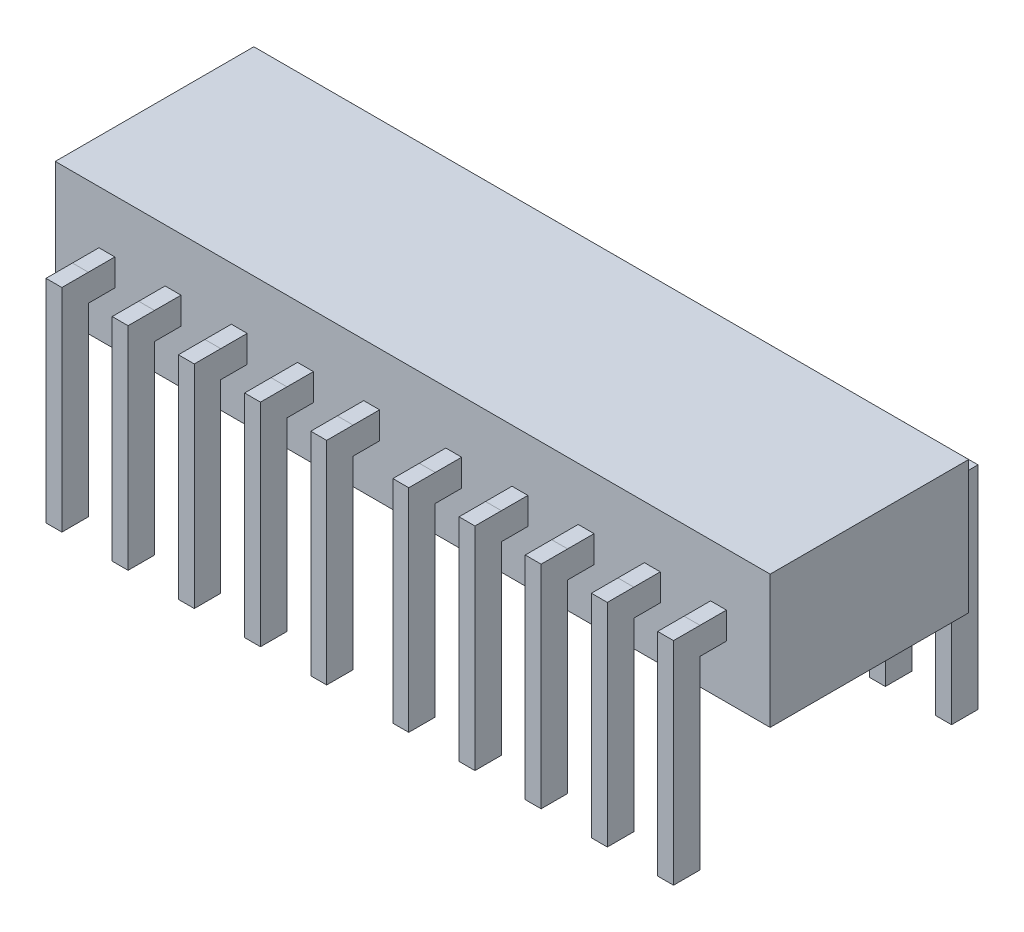
SolidWorks part; units mm, degrees
ref_plane "Front Plane" through (0, 0, 0) normal (0, 0, 1) x (1, 0, 0)
ref_plane "Top Plane" through (0, 0, 0) normal (0, 1, 0) x (1, 0, 0)
ref_plane "Right Plane" through (0, 0, 0) normal (1, 0, 0) x (0, 0, -1)
sketch "Sketch1" plane through (0, 0, 0) normal (0, 1, 0) x (1, 0, 0)
  line L0 (-13500, -3750) -> (13500, -3750)
  line L1 (-13500, -3750) -> (-13500, 3750)
  line L2 (-13500, 3750) -> (13500, 3750)
  line L3 (13500, 3750) -> (13500, -3750)
  line L4 (-11250, 5750) -> (-11850, 5750)
  line L5 (11850, -4750) -> (11850, -5750)
  line L6 (11850, -4750) -> (11250, -4750)
  line L7 (1250, -5750) -> (1250, -3750)
  line L8 (1250, -5750) -> (1850, -5750)
  line L9 (1850, -5750) -> (1850, -3750)
  line L10 (3750, -5750) -> (4350, -5750)
  line L11 (3750, -5750) -> (3750, -3750)
  line L12 (6250, -5750) -> (6850, -5750)
  line L13 (4350, -5750) -> (4350, -3750)
  line L14 (8750, -5750) -> (9350, -5750)
  line L15 (6250, -5750) -> (6250, -3750)
  line L16 (11250, -5750) -> (11850, -5750)
  line L17 (6850, -5750) -> (6850, -3750)
  line L18 (8750, -5750) -> (8750, -3750)
  line L19 (9350, -5750) -> (9350, -3750)
  line L20 (-11850, -5750) -> (-11850, -3750)
  line L21 (-11250, -5750) -> (-11250, -3750)
  line L22 (-9350, -5750) -> (-9350, -3750)
  line L23 (-8750, -5750) -> (-8750, -3750)
  line L24 (-6850, -5750) -> (-6850, -3750)
  line L25 (-11250, -5750) -> (-11850, -5750)
  line L26 (-6250, -5750) -> (-6250, -3750)
  line L27 (-8750, -5750) -> (-9350, -5750)
  line L28 (-4350, -5750) -> (-4350, -3750)
  line L29 (-6250, -5750) -> (-6850, -5750)
  line L30 (-3750, -5750) -> (-3750, -3750)
  line L31 (-3750, -5750) -> (-4350, -5750)
  line L32 (-1850, -5750) -> (-1850, -3750)
  line L33 (-1250, -5750) -> (-1850, -5750)
  line L34 (-1250, -5750) -> (-1250, -3750)
  line L35 (11250, -5750) -> (11250, -3750)
  line L36 (-1250, 5750) -> (-1250, 3750)
  line L37 (-1250, 5750) -> (-1850, 5750)
  line L38 (-1850, 5750) -> (-1850, 3750)
  line L39 (-3750, 5750) -> (-4350, 5750)
  line L40 (-3750, 5750) -> (-3750, 3750)
  line L41 (-6250, 5750) -> (-6850, 5750)
  line L42 (-4350, 5750) -> (-4350, 3750)
  line L43 (-8750, 5750) -> (-9350, 5750)
  line L44 (-6250, 5750) -> (-6250, 3750)
  line L45 (11850, -5750) -> (11850, -3750)
  line L46 (-6850, 5750) -> (-6850, 3750)
  line L47 (-8750, 5750) -> (-8750, 3750)
  line L48 (-9350, 5750) -> (-9350, 3750)
  line L49 (-11250, 5750) -> (-11250, 3750)
  line L50 (-11850, 5750) -> (-11850, 3750)
  line L51 (11850, 5750) -> (11850, 3750)
  line L52 (11250, 5750) -> (11250, 3750)
  line L53 (9350, 5750) -> (9350, 3750)
  line L54 (8750, 5750) -> (8750, 3750)
  line L55 (6850, 5750) -> (6850, 3750)
  line L56 (11250, 5750) -> (11850, 5750)
  line L57 (6250, 5750) -> (6250, 3750)
  line L58 (8750, 5750) -> (9350, 5750)
  line L59 (4350, 5750) -> (4350, 3750)
  line L60 (6250, 5750) -> (6850, 5750)
  line L61 (3750, 5750) -> (3750, 3750)
  line L62 (3750, 5750) -> (4350, 5750)
  line L63 (1850, 5750) -> (1850, 3750)
  line L64 (1250, 5750) -> (1850, 5750)
  line L65 (1250, 5750) -> (1250, 3750)
  line L66 (11250, -5750) -> (11250, -4750)
  line L68 (9350, -4750) -> (9350, -5750)
  line L69 (9350, -4750) -> (8750, -4750)
  line L70 (8750, -5750) -> (9350, -5750)
  line L71 (8750, -5750) -> (8750, -4750)
  line L72 (6850, -4750) -> (6850, -5750)
  line L73 (6850, -4750) -> (6250, -4750)
  line L74 (6250, -5750) -> (6850, -5750)
  line L75 (6250, -5750) -> (6250, -4750)
  line L76 (1850, -4750) -> (1850, -5750)
  line L77 (1850, -4750) -> (1250, -4750)
  line L78 (1250, -5750) -> (1850, -5750)
  line L79 (1250, -5750) -> (1250, -4750)
  line L80 (4350, -4750) -> (4350, -5750)
  line L81 (4350, -4750) -> (3750, -4750)
  line L82 (3750, -5750) -> (4350, -5750)
  line L83 (3750, -5750) -> (3750, -4750)
  line L84 (-1250, -4750) -> (-1250, -5750)
  line L85 (-1250, -4750) -> (-1850, -4750)
  line L86 (-11850, -5750) -> (-11250, -5750)
  line L87 (-9350, -5750) -> (-8750, -5750)
  line L88 (-6850, -5750) -> (-6250, -5750)
  line L89 (-4350, -5750) -> (-3750, -5750)
  line L90 (-1850, -5750) -> (-1250, -5750)
  line L91 (-1850, -5750) -> (-1850, -4750)
  line L92 (-3750, -4750) -> (-3750, -5750)
  line L93 (-3750, -4750) -> (-4350, -4750)
  line L94 (-4350, -5750) -> (-3750, -5750)
  line L95 (-4350, -5750) -> (-4350, -4750)
  line L96 (-6250, -4750) -> (-6250, -5750)
  line L97 (-6250, -4750) -> (-6850, -4750)
  line L98 (-6850, -5750) -> (-6250, -5750)
  line L99 (-6850, -5750) -> (-6850, -4750)
  line L100 (-11250, -4750) -> (-11250, -5750)
  line L101 (-11250, -4750) -> (-11850, -4750)
  line L102 (-11850, -5750) -> (-11250, -5750)
  line L103 (-11850, -5750) -> (-11850, -4750)
  line L104 (-8750, -4750) -> (-8750, -5750)
  line L105 (-8750, -4750) -> (-9350, -4750)
  line L106 (-9350, -5750) -> (-8750, -5750)
  line L107 (-9350, -5750) -> (-9350, -4750)
  line L108 (11850, 5750) -> (11850, 4750)
  line L109 (11850, 5750) -> (11250, 5750)
  line L110 (1250, 4750) -> (1850, 4750)
  line L111 (3750, 4750) -> (4350, 4750)
  line L112 (6250, 4750) -> (6850, 4750)
  line L113 (8750, 4750) -> (9350, 4750)
  line L114 (11250, 4750) -> (11850, 4750)
  line L115 (11250, 4750) -> (11250, 5750)
  line L116 (9350, 5750) -> (9350, 4750)
  line L117 (9350, 5750) -> (8750, 5750)
  line L118 (8750, 4750) -> (9350, 4750)
  line L119 (8750, 4750) -> (8750, 5750)
  line L120 (6850, 5750) -> (6850, 4750)
  line L121 (6850, 5750) -> (6250, 5750)
  line L122 (6250, 4750) -> (6850, 4750)
  line L123 (6250, 4750) -> (6250, 5750)
  line L124 (1850, 5750) -> (1850, 4750)
  line L125 (1850, 5750) -> (1250, 5750)
  line L126 (1250, 4750) -> (1850, 4750)
  line L127 (1250, 4750) -> (1250, 5750)
  line L128 (4350, 5750) -> (4350, 4750)
  line L129 (4350, 5750) -> (3750, 5750)
  line L130 (3750, 4750) -> (4350, 4750)
  line L131 (3750, 4750) -> (3750, 5750)
  line L132 (-1250, 5750) -> (-1250, 4750)
  line L133 (-1250, 5750) -> (-1850, 5750)
  line L134 (-11850, 4750) -> (-11250, 4750)
  line L135 (-9350, 4750) -> (-8750, 4750)
  line L136 (-6850, 4750) -> (-6250, 4750)
  line L137 (-4350, 4750) -> (-3750, 4750)
  line L138 (-1850, 4750) -> (-1250, 4750)
  line L139 (-1850, 4750) -> (-1850, 5750)
  line L140 (-3750, 5750) -> (-3750, 4750)
  line L141 (-3750, 5750) -> (-4350, 5750)
  line L142 (-4350, 4750) -> (-3750, 4750)
  line L143 (-4350, 4750) -> (-4350, 5750)
  line L144 (-6250, 5750) -> (-6250, 4750)
  line L145 (-6250, 5750) -> (-6850, 5750)
  line L146 (-6850, 4750) -> (-6250, 4750)
  line L147 (-6850, 4750) -> (-6850, 5750)
  line L148 (-11250, 5750) -> (-11250, 4750)
  line L149 (-11250, 5750) -> (-11850, 5750)
  line L150 (-11850, 4750) -> (-11250, 4750)
  line L151 (-11850, 4750) -> (-11850, 5750)
  line L152 (-8750, 5750) -> (-8750, 4750)
  line L153 (-8750, 5750) -> (-9350, 5750)
  line L154 (-9350, 4750) -> (-8750, 4750)
  line L155 (-9350, 4750) -> (-9350, 5750)
sketch "Sketch2" plane through (0, 0, 0) normal (0, 0, 1) x (1, 0, 0)
  line L0 (1250, 500) -> (1250, -7500)
  line L1 (-9350, 500) -> (-8750, 500)
  line L2 (1250, -7500) -> (1850, -7500)
  line L3 (1850, -7500) -> (1850, 500)
  line L4 (-11850.0182, 500) -> (-11250, 500)
  line L5 (3750, 500) -> (3750, -7500)
  line L6 (-6850, 500) -> (-6250, 500)
  line L7 (-4350, 500) -> (-3750, 500)
  line L8 (3750, -7500) -> (4350, -7500)
  line L9 (4350, -7500) -> (4350, 500)
  line L10 (-1850, 500) -> (-1250, 500)
  line L11 (6250, 500) -> (6250, -7500)
  line L12 (1250, 500) -> (1850, 500)
  line L13 (6250, -7500) -> (6850, -7500)
  line L14 (6850, -7500) -> (6850, 500)
  line L15 (8750, 500) -> (8750, -7500)
  line L16 (3750, 500) -> (4350, 500)
  line L17 (8750, -7500) -> (9350, -7500)
  line L18 (9350, -7500) -> (9350, 500)
  line L19 (11250, 500) -> (11250, -7500)
  line L20 (6250, 500) -> (6850, 500)
  line L21 (11250, -7500) -> (11850, -7500)
  line L22 (11850, -7500) -> (11850, 500)
  line L24 (-13553.4759, -2500) -> (13446.5241, -2500)
  line L25 (-11850.0182, -7500) -> (-11850.0182, 500)
  line L26 (-11250, -7500) -> (-11850.0182, -7500)
  line L27 (-11250, 500) -> (-11250, -7500)
  line L28 (-9350, -7500) -> (-9350, 500)
  line L29 (-8750, -7500) -> (-9350, -7500)
  line L30 (-8750, 500) -> (-8750, -7500)
  line L31 (-6850, -7500) -> (-6850, 500)
  line L32 (-6250, -7500) -> (-6850, -7500)
  line L33 (-6250, 500) -> (-6250, -7500)
  line L34 (-4350, -7500) -> (-4350, 500)
  line L35 (-3750, -7500) -> (-4350, -7500)
  line L36 (-3750, 500) -> (-3750, -7500)
  line L37 (-1850, -7500) -> (-1850, 500)
  line L38 (-1250, -7500) -> (-1850, -7500)
  line L39 (-1250, 500) -> (-1250, -7500)
  line L40 (13446.5241, -2500) -> (13446.5241, 2500)
  line L41 (8750, 500) -> (9350, 500)
  line L45 (13446.5241, 2500) -> (-13553.4759, 2500)
  line L46 (-13553.4759, 2500) -> (-13553.4759, -2500)
  line L47 (11250, 500) -> (11850, 500)
  point P2 (0, 0)
sketch "Sketch3" plane through (0, 0, 0) normal (1, 0, 0) x (0, 0, -1)
  line L1 (3750, 2500) -> (-3750, 2500)
  line L6 (3750, 500) -> (5750, 500)
  line L7 (5750, 500) -> (5750, -7500)
  line L8 (5750, -7500) -> (4750, -7500)
  line L9 (-3750, 2500) -> (-3750, -2500)
  line L10 (-3750, -2500) -> (3750, -2500)
  line L11 (3750, -2500) -> (3750, 2500)
  line L12 (4750, -7500) -> (4750, -500)
  line L13 (4750, -500) -> (3750, -500)
  line L15 (-4750, -500) -> (-3750, -500)
  line L16 (-4750, -7500) -> (-4750, -500)
  line L17 (-5750, -7500) -> (-4750, -7500)
  line L18 (-5750, 500) -> (-5750, -7500)
  line L19 (-3750, 500) -> (-5750, 500)
extrude "Boss-Extrude3" add sketch "Sketch1" along normal mid plane 5015 contours L3 L2 L1 L0 region at (0, 0, 0)
extrude "Boss-Extrude6" add sketch "Sketch1<14>" against normal blind 7494 and the other way blind 508 separate body contours L35 L16 L5 L6 | L19 L69 L18 L14 | L17 L73 L15 L12 | L13 L81 L11 L10 | L9 L77 L7 L8 | L34 L85 L32 L33 | L30 L93 L28 L31 | L26 L97 L24 L29 | L23 L105 L22 L27 | L21 L101 L20 L25 | L50 L134 L49 L4 | L48 L135 L47 L43 | L46 L136 L44 L41 | L42 L137 L40 L39 | L38 L138 L36 L37 | L65 L110 L63 L64 | L61 L111 L59 L62 | L57 L112 L55 L60 | L54 L113 L53 L58 | L52 L114 L51 L56 region at (-11550, 0, 5250) region at (-11550, 0, -5250) region at (-9050, 0, 5250) region at (-9050, 0, -5250) region at (-6550, 0, 5250) region at (-6550, 0, -5250) region at (-4050, 0, 5250) region at (-4050, 0, -5250) region at (-1550, 0, 5250) region at (-1550, 0, -5250) region at (1550, 0, 5250) region at (1550, 0, -5250) region at (4050, 0, 5250) region at (4050, 0, -5250) region at (6550, 0, 5250) region at (6550, 0, -5250) region at (9050, 0, 5250) region at (9050, 0, -5250) region at (11550, 0, 5250) region at (11550, 0, -5250)
sketch "Sketch1<14>" plane through (0, 0, 0) normal (0, 1, 0) x (1, 0, 0) same geometry as "Sketch1"
extrude "Boss-Extrude8" add sketch "Sketch1<17>" along normal mid plane 1015 contours L6 L45 L0 L35 | L69 L19 L0 L18 | L114 L52 L2 L51 | L113 L54 L2 L53 | L112 L57 L2 L55 | L73 L17 L0 L15 | L81 L13 L0 L11 | L77 L9 L0 L7 | L85 L34 L0 L32 | L138 L38 L2 L36 | L110 L65 L2 L63 | L111 L61 L2 L59 | L93 L30 L0 L28 | L97 L26 L0 L24 | L137 L42 L2 L40 | L136 L46 L2 L44 | L135 L48 L2 L47 | L105 L23 L0 L22 | L101 L21 L0 L20 | L134 L50 L2 L49 region at (-11550, 0, 4250) region at (-11550, 0, -4250) region at (-9050, 0, 4250) region at (-9050, 0, -4250) region at (-6550, 0, 4250) region at (-6550, 0, -4250) region at (-4050, 0, 4250) region at (-4050, 0, -4250) region at (-1550, 0, 4250) region at (-1550, 0, -4250) region at (1550, 0, 4250) region at (1550, 0, -4250) region at (4050, 0, 4250) region at (4050, 0, -4250) region at (6550, 0, 4250) region at (6550, 0, -4250) region at (9050, 0, 4250) region at (9050, 0, -4250) region at (11550, 0, 4250) region at (11550, 0, -4250)
sketch "Sketch1<17>" plane through (0, 0, 0) normal (0, 1, 0) x (1, 0, 0) same geometry as "Sketch1"
